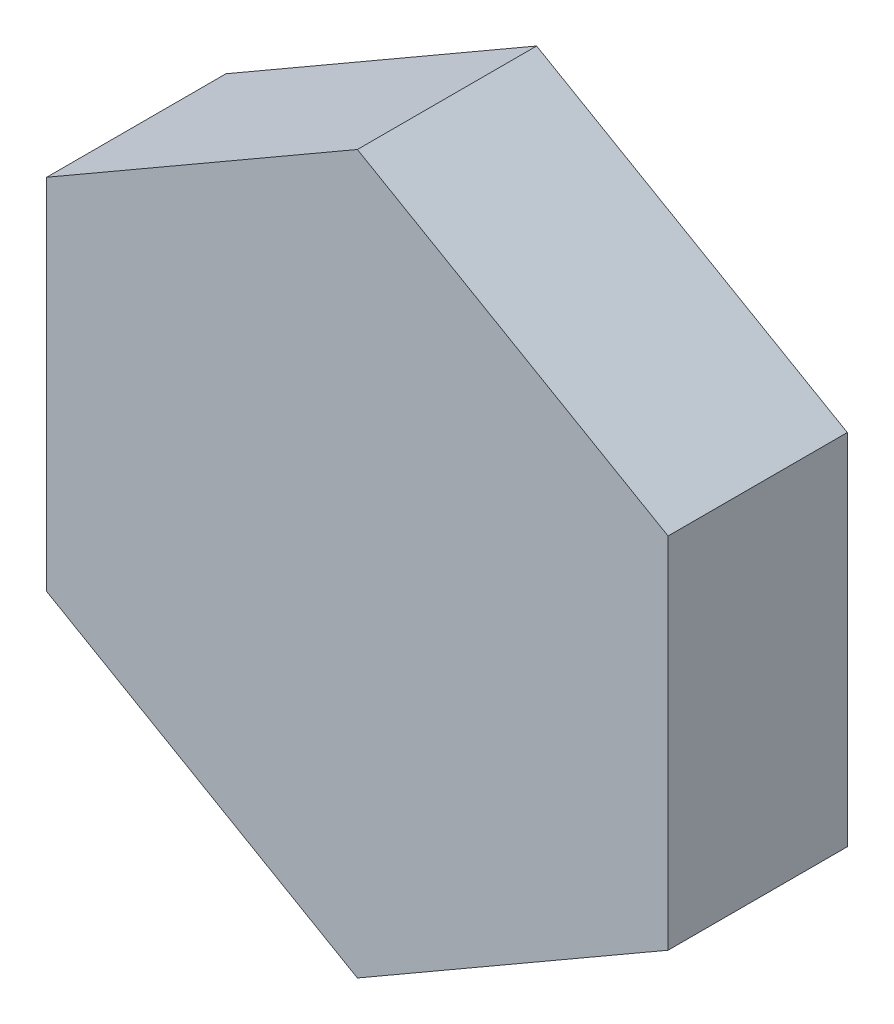
SolidWorks part; units mm, degrees
ref_plane "Front Plane" through (0, 0, 0) normal (0, 0, 1) x (1, 0, 0)
ref_plane "Top Plane" through (0, 0, 0) normal (0, 1, 0) x (1, 0, 0)
ref_plane "Right Plane" through (0, 0, 0) normal (1, 0, 0) x (0, 0, -1)
sketch "Sketch4" plane through (0, 0, 0) normal (0, 0, 1) x (1, 0, 0)
  line L1 (0, -270.1999) -> (234, -135.1)
  line L2 (234, -135.1) -> (234, 135.1)
  line L3 (234, 135.1) -> (0, 270.1999)
  line L4 (0, 270.1999) -> (-234, 135.1)
  line L5 (-234, 135.1) -> (-234, -135.1)
  line L6 (-234, -135.1) -> (0, -270.1999)
  circle A0 centre (0, 0) radius 234 construction
  dimension "D1" = 468
extrude "Boss-Extrude1" add sketch "Sketch4" along normal blind 135
